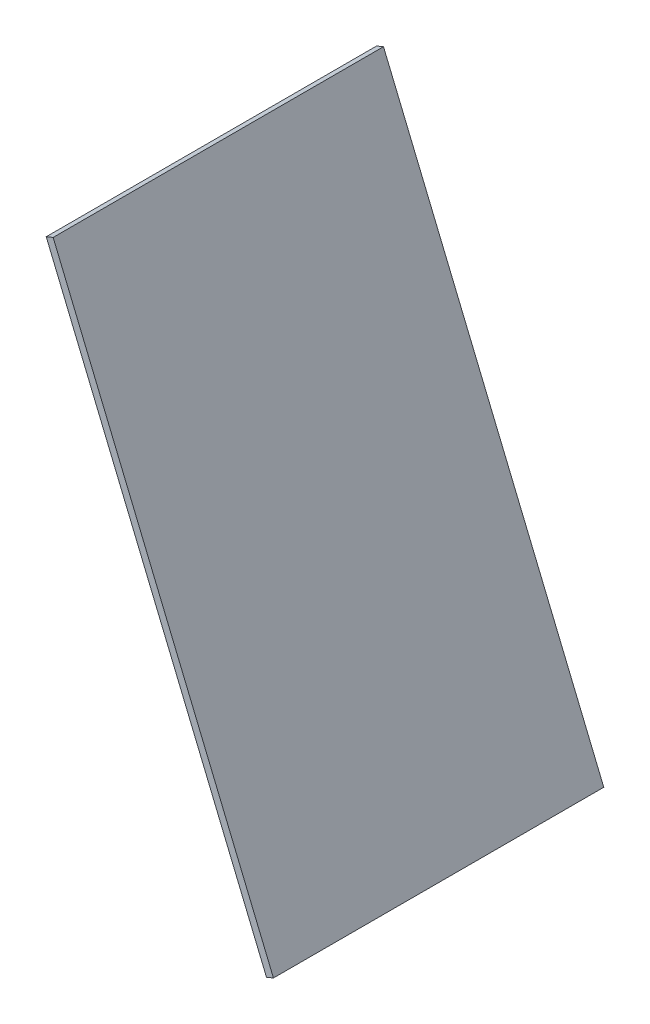
SolidWorks part; units mm, degrees
ref_plane "Front Plane" through (0, 0, 0) normal (0, 0, 1) x (1, 0, 0)
ref_plane "Top Plane" through (0, 0, 0) normal (0, 1, 0) x (1, 0, 0)
ref_plane "Right Plane" through (0, 0, 0) normal (1, 0, 0) x (0, 0, -1)
sketch "Sketch1" plane through (-144.367, -59.8657, 0) normal (-0.9237, -0.383, 0) x (0, 0, 1)
  line L0 (-65.453, -298.979) -> (74.247, -298.979) construction
  line L1 (-65.453, -55.779) -> (74.247, -55.779) construction
  line L2 (-65.453, -298.979) -> (74.247, -298.979)
  line L3 (-65.453, -55.779) -> (74.247, -55.779)
  line L4 (74.247, -55.779) -> (74.247, -298.979)
  line L5 (-65.453, -298.979) -> (-65.453, -55.779)
extrude "Boss-Extrude1" add sketch "Sketch1" along normal blind 3.175
